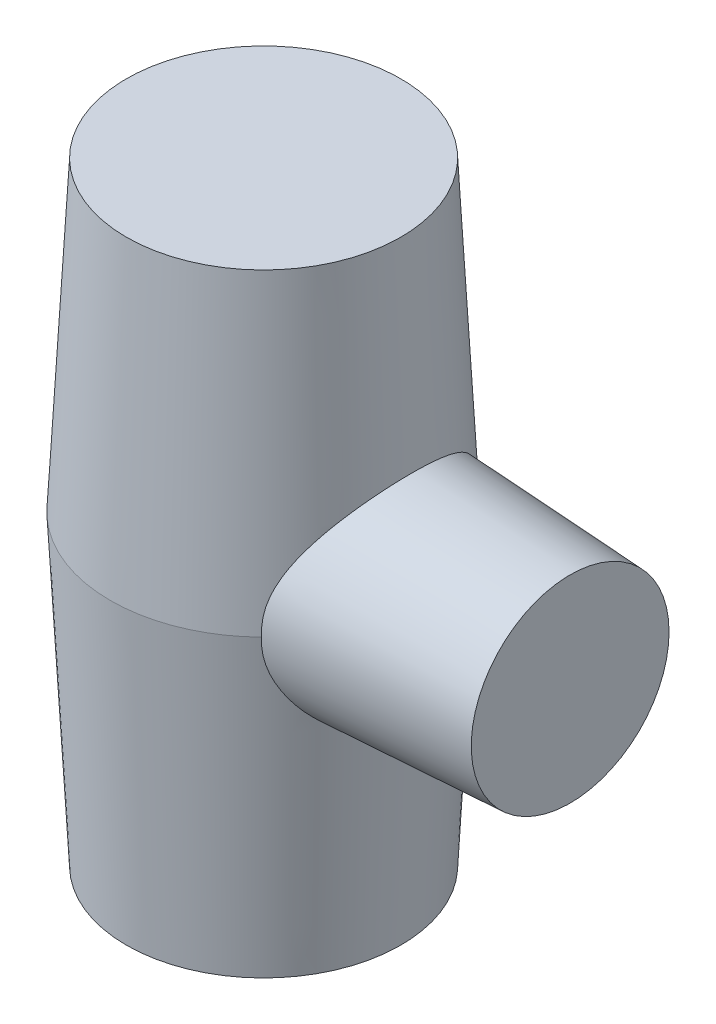
SolidWorks part; units mm, degrees
note: '?' marks a value the reader was unsure of.
ref_plane "Front Plane" through (0, 0, 0) normal (0, 0, 1) x (1, 0, 0)
ref_plane "Top Plane" through (0, 0, 0) normal (0, 1, 0) x (1, 0, 0)
ref_plane "Right Plane" through (0, 0, 0) normal (1, 0, 0) x (0, 0, -1)
sketch "Sketch1" plane through (0, 0, 0) normal (0, 1, 0) x (1, 0, 0)
  circle A0 centre (0, 0) radius 1.27
  dimension "D1" = 2.54
extrude "Boss-Extrude1" add sketch "Sketch1" along normal mid plane 5.08 draft 3
sketch "Sketch2" plane through (0, 0, 0) normal (1, 0, 0) x (0, 0, -1)
  line L0 (-1.27, 0) -> (1.27, 0) construction
  circle A0 centre (0, 0) radius 0.9525
  dimension "D1" = 1.905
extrude "Boss-Extrude2" add sketch "Sketch2" along normal blind 2.54 draft 3
other "CPoint1" parameters "Diameter"=0.635, "StubLength"=0.9525
ref_axis "Axis1" through (0, 12.54, 0) along (0, -1, 0)?
other "CPoint2" parameters "Diameter"=0.635, "StubLength"=0.9525
ref_axis "Axis2" through (12.54, 0, 0) along (-1, 0, 0)?
other "CPoint3" parameters "Diameter"=0.635, "StubLength"=0.9525
ref_axis "Axis3" through (0, -12.54, 0) along (0, 1, 0)?
